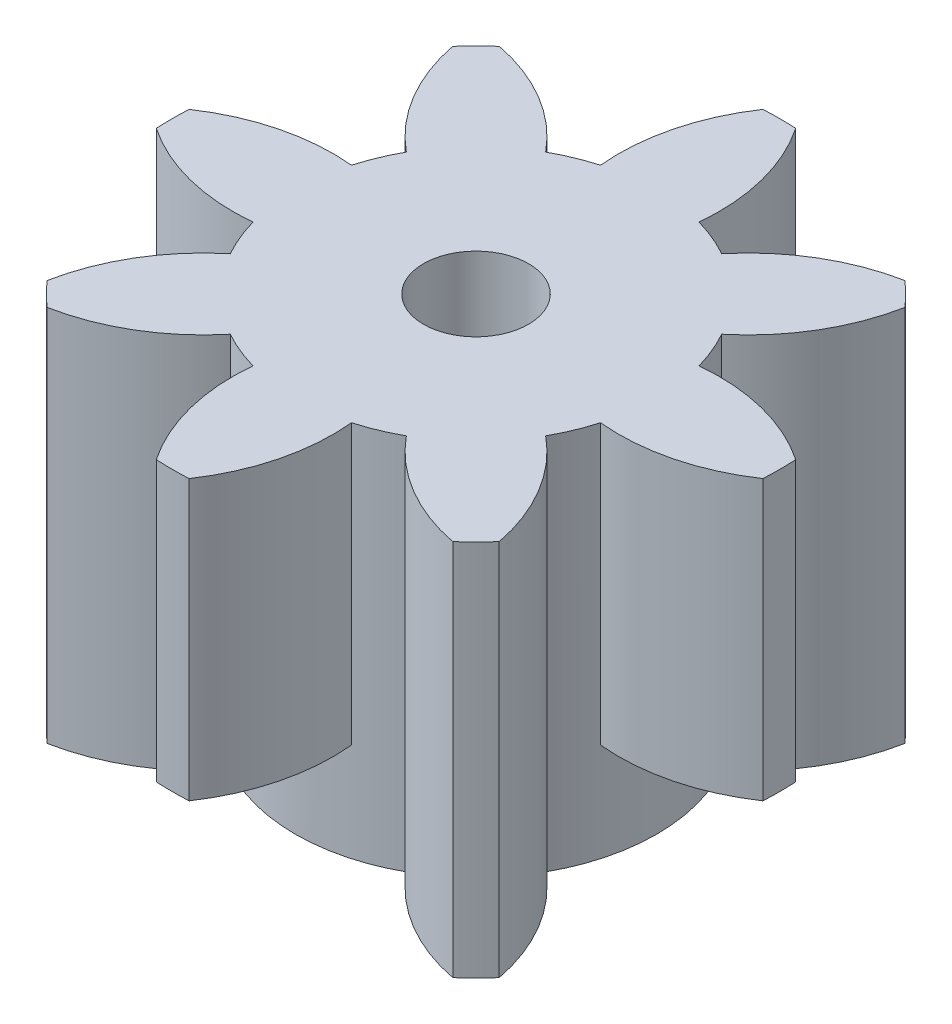
SolidWorks part; units mm, degrees
ref_plane "Front Plane" through (0, 0, 0) normal (0, 0, 1) x (1, 0, 0)
ref_plane "Top Plane" through (0, 0, 0) normal (0, 1, 0) x (1, 0, 0)
ref_plane "Right Plane" through (0, 0, 0) normal (1, 0, 0) x (0, 0, -1)
sketch "Sketch1" plane through (0, 0, 0) normal (0, 1, 0) x (1, 0, 0)
  line L0 (0, 0) -> (0, 18.5) construction
  line L1 (0, 0) -> (2.8151, 14.1527) construction
  line L2 (0, 0) -> (-18.5, 0) construction
  line L3 (-20.702, 0) -> (-56, 0) construction
  line L4 (0, 0) -> (56, 0) construction
  circle A0 centre (0, 0) radius 18.5
  circle A1 centre (0, 0) radius 16 construction
  circle A2 centre (0, 0) radius 15.035 construction
  circle A3 centre (0, 0) radius 11
  arc A4 (1, 18.473) -> (3, 10.583) centre (-8.9427, 11.7541) cw
  arc A5 (-1, 18.473) -> (-3, 10.583) centre (8.9427, 11.7541) ccw
  arc A6 (12.3552, 13.7695) -> (5.362, 9.6046) centre (14.6349, 1.988) ccw
  arc A7 (13.7695, 12.3552) -> (9.6046, 5.362) centre (1.988, 14.6349) cw
  arc A8 (18.473, 1) -> (10.583, 3) centre (11.7541, -8.9427) ccw
  arc A9 (18.473, -1) -> (10.583, -3) centre (11.7541, 8.9427) cw
  arc A10 (13.7695, -12.3552) -> (9.6046, -5.362) centre (1.988, -14.6349) ccw
  arc A11 (12.3552, -13.7695) -> (5.362, -9.6046) centre (14.6349, -1.988) cw
  arc A12 (1, -18.473) -> (3, -10.583) centre (-8.9427, -11.7541) ccw
  arc A13 (-1, -18.473) -> (-3, -10.583) centre (8.9427, -11.7541) cw
  arc A14 (-12.3552, -13.7695) -> (-5.362, -9.6046) centre (-14.6349, -1.988) ccw
  arc A15 (-13.7695, -12.3552) -> (-9.6046, -5.362) centre (-1.988, -14.6349) cw
  arc A16 (-18.473, -1) -> (-10.583, -3) centre (-11.7541, 8.9427) ccw
  arc A17 (-18.473, 1) -> (-10.583, 3) centre (-11.7541, -8.9427) cw
  arc A18 (-13.7695, 12.3552) -> (-9.6046, 5.362) centre (-1.988, 14.6349) ccw
  arc A19 (-12.3552, 13.7695) -> (-5.362, 9.6046) centre (-14.6349, 1.988) cw
  circle A20 centre (0, 0) radius 3.2
  dimension "D1" = 37
  dimension "D2" = 32
  dimension "D3" = 30.07
  dimension "D4" = 22
  dimension "D6" = 12
  dimension "D8" = 6.4
  dimension "D9" = 56
  dimension "D10" = 56
  dimension "D11" = 3
  dimension "D5" = 11.25
  dimension "D7" = 1
extrude "Boss-Extrude1" add sketch "Sketch1" along normal blind 17 and the other way blind 6 contours A3 A20 | A3 A0 | A3 A0 | A3 A0 | A3 A0 | A3 A0 | A3 A0 | A3 A0 | A3 A0 region at (14.1635, 0, 0) region at (10.0151, 0, -10.0151) region at (10.5871, 0, -1.4716) region at (10.0151, 0, 10.0151) region at (0, 0, -14.1635) region at (0, 0, 14.1635) region at (-10.0151, 0, -10.0151) region at (-10.0151, 0, 10.0151) region at (-14.1635, 0, 0)
extrude "Cut-Extrude1" cut sketch "Sketch1<7>" against normal blind 10 contours A3 A0 | A3 A0 | A3 A0 | A3 A0 region at (14.1635, 0, 0) region at (0, 0, -14.1635) region at (0, 0, 14.1635) region at (-14.1635, 0, 0)
sketch "Sketch1<7>" plane through (0, 0, 0) normal (0, 1, 0) x (1, 0, 0) same geometry as "Sketch1"
